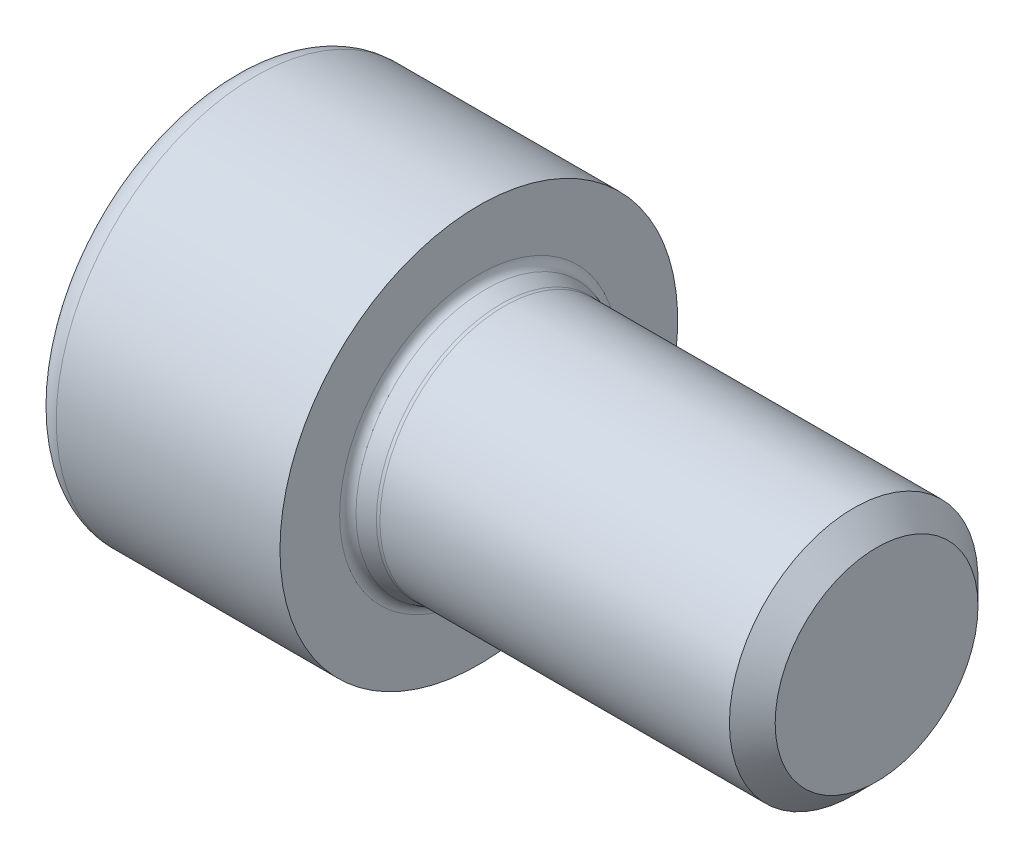
SolidWorks part; units mm, degrees
note: '?' marks a value the reader was unsure of.
ref_plane "前视基准面" through (0, 0, 0) normal (0, 0, 1) x (1, 0, 0)
ref_plane "上视基准面" through (0, 0, 0) normal (0, 1, 0) x (1, 0, 0)
ref_plane "右视基准面" through (0, 0, 0) normal (1, 0, 0) x (0, 0, -1)
sketch "草图1" plane through (0, 0, 0) normal (0, 0, 1) x (1, 0, 0)
  line L0 (-1.6906, 0) -> (-4, 4)
  line L1 (-4, 4) -> (-10, 4)
  line L2 (-10, 4) -> (-10, 7)
  line L3 (-9, 8) -> (0, 8)
  line L4 (0, 8) -> (0, 5.6)
  line L5 (0.2772, 5.2193) -> (0.8972, 5.0193)
  line L6 (1.02, 5) -> (15.08, 5)
  line L7 (15.08, 5) -> (16, 4.08)
  line L8 (16, 4.08) -> (16, 0)
  line L9 (16, 0) -> (-1.6906, 0)
  line L10 (16, 0) -> (-1.6906, 0) construction
  arc A0 (-10, 7) -> (-9, 8) centre (-9, 7) cw
  arc A1 (0, 5.6) -> (0.2772, 5.2193) centre (0.4, 5.6) ccw
  arc A2 (0.8972, 5.0193) -> (1.02, 5) centre (1.02, 5.4) ccw
revolve "旋转1" add sketch "草图1" angle 360 about L10
cosmetic thread "装饰螺纹线1" parameters "D1"=4.5, "D2"=8.16
ref_plane "基准面4" through (-4, 0, 0) normal (1, 0, 0) x (0, 0, -1)
sketch "草图2" plane through (-4, 0, 0) normal (1, 0, 0) x (0, 0, -1)
  line L0 (-4, 2.3094) -> (-4, -2.3094)
  line L1 (-4, -2.3094) -> (0, -4.6188)
  line L2 (0, -4.6188) -> (4, -2.3094)
  line L3 (4, -2.3094) -> (4, 2.3094)
  line L4 (4, 2.3094) -> (0, 4.6188)
  line L5 (0, 4.6188) -> (-4, 2.3094)
extrude "切除-拉伸1" cut sketch "草图2" against normal blind 10
ref_plane "基准面5" through (0, 0, 0) normal (1, 0, 0) x (0, 0, -1)
ref_plane "基准面6" through (16, 0, 0) normal (1, 0, 0) x (0, 0, -1)
ref_plane "基准面7" through (-10, 0, 0) normal (1, 0, 0) x (0, 0, -1)
ref_plane "IP1 XY" through (0, 0, 0) normal (1, 0, 0) x (0, 0, -1)
ref_plane "IP1 XZ" through (0, 0, 0) normal (0, -1, 0) x (-1, 0, 0)
ref_plane "IP1 YZ" through (0, 0, 0) normal (0, 0, -1) x (-1, 0, 0)
ref_axis "IP1 X" through (0, 0, 80.9) along (0, 0, -1)?
ref_axis "IP1 Y" through (0, -50, 0) along (0, 1, 0)?
ref_axis "IP1 Z" through (80.9, 0, 0) along (-1, 0, 0)?
sketch3d "IP1"
  point P0 (0, 0, 0)
ref_plane "IP3 XY" through (16, 0, 0) normal (1, 0, 0) x (0, 0, -1)
ref_plane "IP3 XZ" through (0, 0, 0) normal (0, -1, 0) x (-1, 0, 0)
ref_plane "IP3 YZ" through (0, 0, 0) normal (0, 0, -1) x (-1, 0, 0)
ref_axis "IP3 X" through (16, 0, 80.9) along (0, 0, -1)?
ref_axis "IP3 Y" through (16, -50, 0) along (0, 1, 0)?
ref_axis "IP3 Z" through (80.9, 0, 0) along (-1, 0, 0)?
sketch3d "IP3"
  point P0 (16, 0, 0)
ref_plane "IP2 XY" through (-10, 0, 0) normal (1, 0, 0) x (0, 0, -1)
ref_plane "IP2 XZ" through (0, 0, 0) normal (0, -1, 0) x (-1, 0, 0)
ref_plane "IP2 YZ" through (0, 0, 0) normal (0, 0, -1) x (-1, 0, 0)
ref_axis "IP2 X" through (-10, 0, 80.9) along (0, 0, -1)?
ref_axis "IP2 Y" through (-10, -50, 0) along (0, 1, 0)?
ref_axis "IP2 Z" through (80.9, 0, 0) along (-1, 0, 0)?
sketch3d "IP2"
  point P0 (-10, 0, 0)
ref_plane "IP4 XY" through (0, 0, 0) normal (1, 0, 0) x (0, 0, -1)
ref_plane "IP4 XZ" through (0, 0, 0) normal (0, -1, 0) x (-1, 0, 0)
ref_plane "IP4 YZ" through (0, 0, 0) normal (0, 0, -1) x (-1, 0, 0)
ref_axis "IP4 X" through (0, 0, 80.9) along (0, 0, -1)?
ref_axis "IP4 Y" through (0, -50, 0) along (0, 1, 0)?
ref_axis "IP4 Z" through (80.9, 0, 0) along (-1, 0, 0)?
sketch3d "IP4"
  point P0 (0, 0, 0)
sketch "草图3" plane through (0, 0, 0) normal (1, 0, 0) x (0, 0, -1)
  circle A0 centre (0, 0) radius 6
extrude "凸台-拉伸1" add sketch "草图3" against normal blind 5 separate body
other "删除面1" face at (-5, 0, -6)
